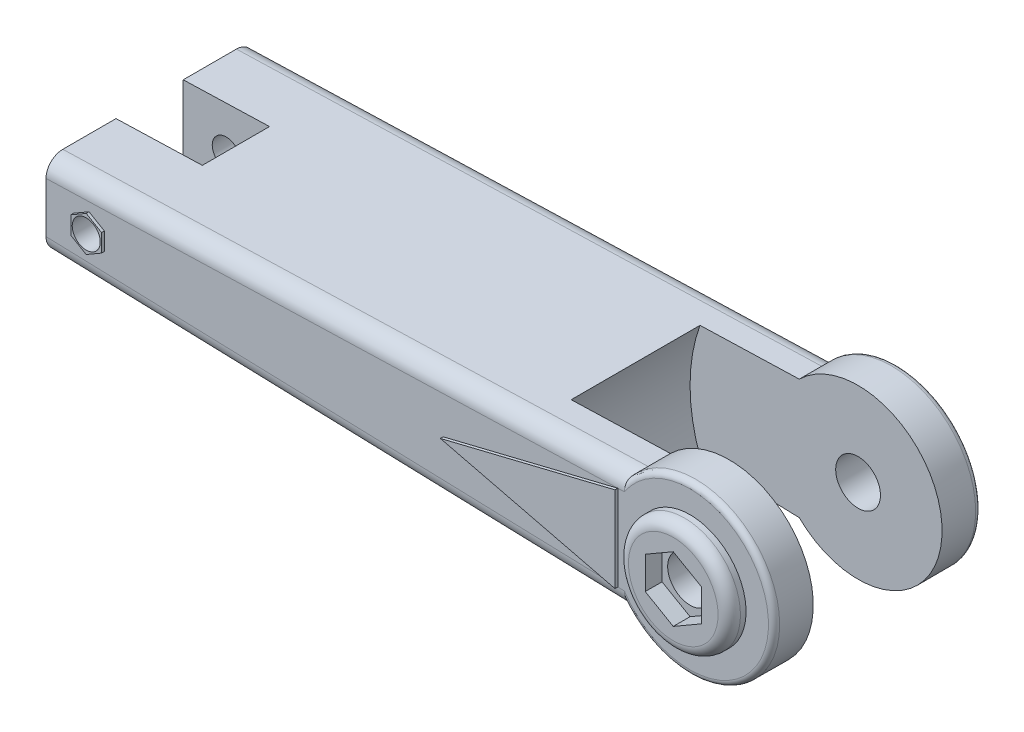
SolidWorks part; units mm, degrees
ref_plane "Ön Düzlem" through (0, 0, 0) normal (0, 0, 1) x (1, 0, 0)
ref_plane "Üst Düzlem" through (0, 0, 0) normal (0, 1, 0) x (1, 0, 0)
ref_plane "Sağ Düzlem" through (0, 0, 0) normal (1, 0, 0) x (0, 0, -1)
sketch "Sketch1" plane through (0, 0, 0) normal (0, 0, 1) x (1, 0, 0)
  line L0 (10.5, 10.7121) -> (115, 7.5)
  line L1 (115, 7.5) -> (115, -7.5)
  line L3 (10.5, -10.7121) -> (115, -7.5)
  arc A0 (10.5, 10.7121) -> (10.5, -10.7121) centre (0, 0) ccw
  dimension "D1" = 30
  dimension "D2" = 15
  dimension "D5" = 10.5
extrude "Boss-Extrude1" add sketch "Sketch1" along normal mid plane 37
sketch "Sketch3" plane through (0, 0, 0) normal (0, 0, 1) x (1, 0, 0)
  circle A0 centre (0, 0) radius 30
  dimension "D1" = 60
extrude "Cut-Extrude2" cut sketch "Sketch3" against normal mid plane 23
sketch "Sketch4" plane through (0, 0, 0) normal (0, 0, 1) x (1, 0, 0)
  line L0 (114.9483, 12.5) -> (115, 7.5)
  line L1 (115, 7.5) -> (115, -12.5)
  line L2 (114.9483, 12.5) -> (99.5883, 12.5)
  line L3 (99.5883, 12.5) -> (99.5883, -12.5)
  line L4 (99.5883, -12.5) -> (115, -12.5)
  dimension "D1" = 5
  dimension "D2" = 20
  dimension "D3" = 15.36
extrude "Cut-Extrude3" cut sketch "Sketch4" against normal mid plane 12
sketch "Sketch5" plane through (0, 0, 18.5) normal (0, 0, 1) x (1, 0, 0)
  circle A0 centre (0, 0) radius 4
  dimension "D1" = 8
extrude "Cut-Extrude4" cut sketch "Sketch5" against normal through all
sketch "Sketch6" plane through (0, 0, 18.5) normal (0, 0, 1) x (1, 0, 0)
  line L1 (0, -5.7735) -> (5, -2.8868)
  line L2 (5, -2.8868) -> (5, 2.8868)
  line L3 (5, 2.8868) -> (0, 5.7735)
  line L4 (0, 5.7735) -> (-5, 2.8868)
  line L5 (-5, 2.8868) -> (-5, -2.8868)
  line L6 (-5, -2.8868) -> (0, -5.7735)
  circle A0 centre (0, 0) radius 10
  circle A1 centre (0, 0) radius 5 construction
  dimension "D1" = 20
  dimension "D2" = 10
extrude "Boss-Extrude2" add sketch "Sketch6" along normal blind 3
fillet "Fillet1" radius 2 1 edges at (10, 0, 21.5)
mirror "Mirror1" about plane through (0, 0, 0) normal (0, 0, 1) of "Fillet1", "Boss-Extrude2"
sketch "Sketch7" plane through (0, 0, 18.5) normal (0, 0, 1) x (1, 0, 0)
  line L0 (115, 0) -> (107.32, 0)
  line L1 (115, -7.5) -> (115, 7.5) construction
  circle A0 centre (107.32, 0) radius 2.5
  dimension "D2" = 5
  dimension "D1" = 7.68
extrude "Cut-Extrude5" cut sketch "Sketch7" against normal through all contours A0 region at (104.8907, 0, 18.5)
sketch "Sketch8" plane through (0, 0, 18.5) normal (0, 0, 1) x (1, 0, 0)
  line L1 (107.32, -3.1754) -> (110.07, -1.5877)
  line L2 (110.07, -1.5877) -> (110.07, 1.5877)
  line L3 (110.07, 1.5877) -> (107.32, 3.1754)
  line L4 (107.32, 3.1754) -> (104.57, 1.5877)
  line L5 (104.57, 1.5877) -> (104.57, -1.5877)
  line L6 (104.57, -1.5877) -> (107.32, -3.1754)
  circle A0 centre (107.32, 0) radius 2.75 construction
  dimension "D1" = 5.5
extrude "Boss-Extrude3" add sketch "Sketch8" along normal blind 0.5
mirror "Mirror2" about plane through (0, 0, 0) normal (0, 0, 1) of "Boss-Extrude3"
sketch "Sketch9" plane through (0, 0, 6) normal (0, 0, -1) x (-1, 0, 0)
  circle A0 centre (-107.32, 0) radius 2.5
extrude "Cut-Extrude6" cut sketch "Sketch9" against normal blind 15.5
sketch "Sketch10" plane through (0, 0, -6) normal (0, 0, 1) x (1, 0, 0)
  circle A0 centre (107.32, 0) radius 2.5
extrude "Cut-Extrude7" cut sketch "Sketch10" against normal blind 15.5
fillet "Fillet2" radius 3 4 edges at (62.75, -9.1061, 18.5) (62.75, 9.1061, 18.5) (62.75, -9.1061, -18.5) (62.75, 9.1061, -18.5)
sketch "Sketch11" plane through (0, 0, 18.5) normal (0, 0, 1) x (1, 0, 0)
  line L0 (12.9105, 7.6366) -> (44.0964, 0)
  line L1 (44.0964, 0) -> (12.9105, -7.6366)
  line L2 (12.9105, -7.6366) -> (12.9105, 7.6366)
extrude "Boss-Extrude4" add sketch "Sketch11" along normal blind 0.5
mirror "Mirror3" about plane through (0, 0, 0) normal (0, 0, 1) of "Boss-Extrude4"
fillet "Fillet3" radius 1 2 edges at (-15, 0, -18.5) (-15, 0, 18.5)
move or copy body "Body-Move/Copy1" bodies to move or copy 114 copy no rotation origin (50, 0, 0) rotation axis (0, 1, 0) rotation angle 180
ref_point "Point1"
